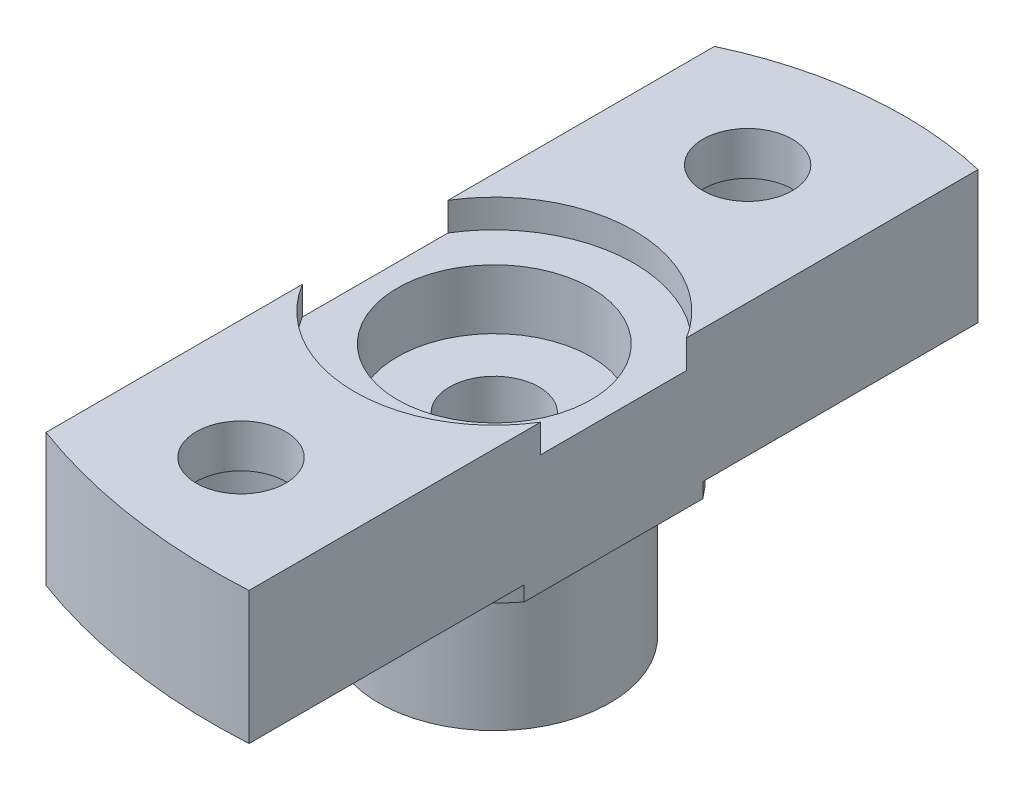
SolidWorks part; units mm, degrees
ref_plane "Front Plane" through (0, 0, 0) normal (0, 0, 1) x (1, 0, 0)
ref_plane "Top Plane" through (0, 0, 0) normal (0, 1, 0) x (1, 0, 0)
ref_plane "Right Plane" through (0, 0, 0) normal (1, 0, 0) x (0, 0, -1)
sketch "Sketch1" plane through (0, 0, 0) normal (0, 1, 0) x (1, 0, 0)
  line L0 (2.032, 6.2129) -> (2.032, -6.2129)
  line L1 (2.032, 0) -> (-3.7, 0) construction
  line L2 (-2.032, 6.2064) -> (-2.032, -6.2064)
  line L3 (2.032, 6.2129) -> (0.4612, 6.8042)
  line L4 (2.032, -6.2129) -> (0.4612, -6.8042)
  circle A0 centre (0, 4.318) radius 0.762
  circle A1 centre (0, -4.318) radius 0.762
  circle A2 centre (0, 4.318) radius 1.524
  circle A3 centre (0, -4.318) radius 1.524
  circle A4 centre (0, 0) radius 0.9525 construction
  circle A5 centre (0, 4.318) radius 1.27
  circle A6 centre (0, -4.318) radius 1.27
  circle A7 centre (0, 0) radius 2.3813
  arc A8 (0.4612, 6.8042) -> (-2.032, 6.2064) centre (-0.3441, 4.6648) ccw
  arc A9 (0.4612, -6.8042) -> (-2.032, -6.2064) centre (-0.3441, -4.6648) cw
  point P14 (2.032, 0)
  point P19 (-2.032, 0)
  dimension "D1" = 1.524
  dimension "D2" = 3.048
  dimension "D5" = 2.54
  dimension "D8" = 4.7625
  dimension "D3" = 4.318
  dimension "D4" = 4.318
  dimension "D6" = 2.032
  dimension "D7" = 2.032
extrude "Boss-Extrude1" add sketch "Sketch1" along normal blind 2.032 contours A9 L4 L0 A7 L2 A3 | L3 A8 L2 A7 L0 A2 | L0 A7 L2 | A3 A6 | A6 A1 | A2 A5 | A5 A0 region at (1.9619, 0, -3.7272) region at (0, 0, 0) region at (1.9619, 0, 3.7272) region at (-1.4809, 0, -4.318) region at (-1.4809, 0, 4.318) region at (-1.2341, 0, -4.318) region at (-1.2341, 0, 4.318)
extrude "Cut-Extrude1" cut sketch "Sketch1<3>" along normal blind 1.524 contours A6 A1 | A5 A0 region at (-1.2341, 0, -4.318) region at (-1.2341, 0, 4.318)
sketch "Sketch1<3>" plane through (0, 0, 0) normal (0, 1, 0) x (1, 0, 0) same geometry as "Sketch1"
sketch "Sketch3" plane through (0, 2.032, 0) normal (0, 1, 0) x (1, 0, 0)
  circle A0 centre (0, 0) radius 2.3813
  circle A1 centre (0, 0) radius 1.651
  line M3 (2.032, -6.2129) -> (2.032, 6.2129)
  line M6 (-2.032, 6.2064) -> (-2.032, -6.2064)
  dimension "D1" = 4.7625
  dimension "D2" = 3.302
extrude "Cut-Extrude2" cut sketch "Sketch3" against normal blind 0.254 contours A0 A1 M3 M6 | A1 region at (1.9694, 2.032, 0) region at (0, 2.032, 0)
extrude "Cut-Extrude3" cut sketch "Sketch3<3>" against normal up to surface (2.032 mm away) contours A1 region at (0, 2.032, 0) up to face at (0, 0, 5.588)
sketch "Sketch3<3>" plane through (0, 2.032, 0) normal (0, 1, 0) x (1, 0, 0) same geometry as "Sketch3"
sketch "Sketch4" plane through (0, 0, 0) normal (0, -1, 0) x (1, 0, 0)
  circle A0 centre (0, 0) radius 1.651
  circle A1 centre (0, 0) radius 2.54
  circle A2 centre (0, 0) radius 1.9685
  circle A3 centre (0, 0) radius 0.762
  circle M1 centre (0, 0) radius 1.651
  line M5 (-2.032, 6.2064) -> (-2.032, -6.2064)
  line M8 (2.032, -6.2129) -> (2.032, 6.2129)
  dimension "D1" = 5.08
  dimension "D2" = 3.937
  dimension "D3" = 1.524
extrude "Boss-Extrude2" add sketch "Sketch4" along normal blind 0.254 contours A1 A2 M8 M5 region at (2.0255, 0, 0)
extrude "Boss-Extrude3" add sketch "Sketch4<3>" along normal blind 2.54 and the other way blind 0.762 contours A2 M1 | A3 M1 region at (-1.6043, 0, 0) region at (-1.9128, 0, 0)
sketch "Sketch4<3>" plane through (0, 0, 0) normal (0, -1, 0) x (1, 0, 0) same geometry as "Sketch4"
sketch "Sketch6" plane through (0, 0, 0) normal (0, -1, 0) x (1, 0, 0)
  line L0 (-2.032, 1.524) -> (-2.032, 6.2064) construction
  line L1 (-2.032, -6.2064) -> (-2.032, -1.524) construction
  line L2 (-2.032, 5.6094) -> (-2.032, 6.2064)
  line L3 (-2.032, -5.7849) -> (-2.032, -6.2064)
  arc A0 (2.032, 6.2129) -> (-2.032, 5.6094) centre (1.4404, -3.7895) ccw
  arc A1 (2.032, -6.2129) -> (-2.032, -5.7849) centre (0.615, -0.1588) cw
  arc A2 (-2.032, 6.2064) -> (2.032, 6.2129) centre (0, 6.2064) cw
  arc A4 (-2.032, -6.2064) -> (2.032, -6.2129) centre (0.0017, -5.156) ccw
extrude "Cut-Extrude4" cut sketch "Sketch6" against normal up to surface (2.032 mm away) up to face at (0.0739, 2.032, 4.6457)
fillet "Fillet1" [suppressed] radius 1.778
sketch "Sketch10" plane through (0, 2.032, 0) normal (0, 1, 0) x (1, 0, 0)
  line L0 (-2.032, -5.6094) -> (-2.032, 5.7849)
  line L1 (2.032, -6.2129) -> (2.032, 6.2129)
  arc A0 (2.032, -6.2129) -> (-2.032, -5.6094) centre (1.4404, 3.7895) cw
  arc A1 (-2.032, 5.7849) -> (2.032, 6.2129) centre (0.615, 0.1588) cw
  arc A2 (-2.032, -1.2415) -> (2.032, -1.2415) centre (0, 0) ccw
  arc A3 (-2.032, 1.2415) -> (2.032, 1.2415) centre (0, 0) cw
  circle A4 centre (0, -4.318) radius 0.762
  circle A5 centre (0, 4.318) radius 0.762
  arc M3 (-2.032, -5.6094) -> (2.032, -6.2129) centre (1.4404, 3.7895) ccw
  line M4 (2.032, -6.2129) -> (2.032, -1.2415)
  arc M5 (2.032, -1.2415) -> (-2.032, -1.2415) centre (0, 0) cw
  line M6 (-2.032, -1.2415) -> (-2.032, -5.6094)
  circle M7 centre (0, -4.318) radius 0.762
extrude "Boss-Extrude4" add sketch "Sketch10" along normal blind 0.2286 contours M6 M3 M4 M5 M7 | L0 A3 L1 A1 A5 region at (-1.9677, 2.032, 3.4255) region at (-1.9665, 2.032, -3.5132)
